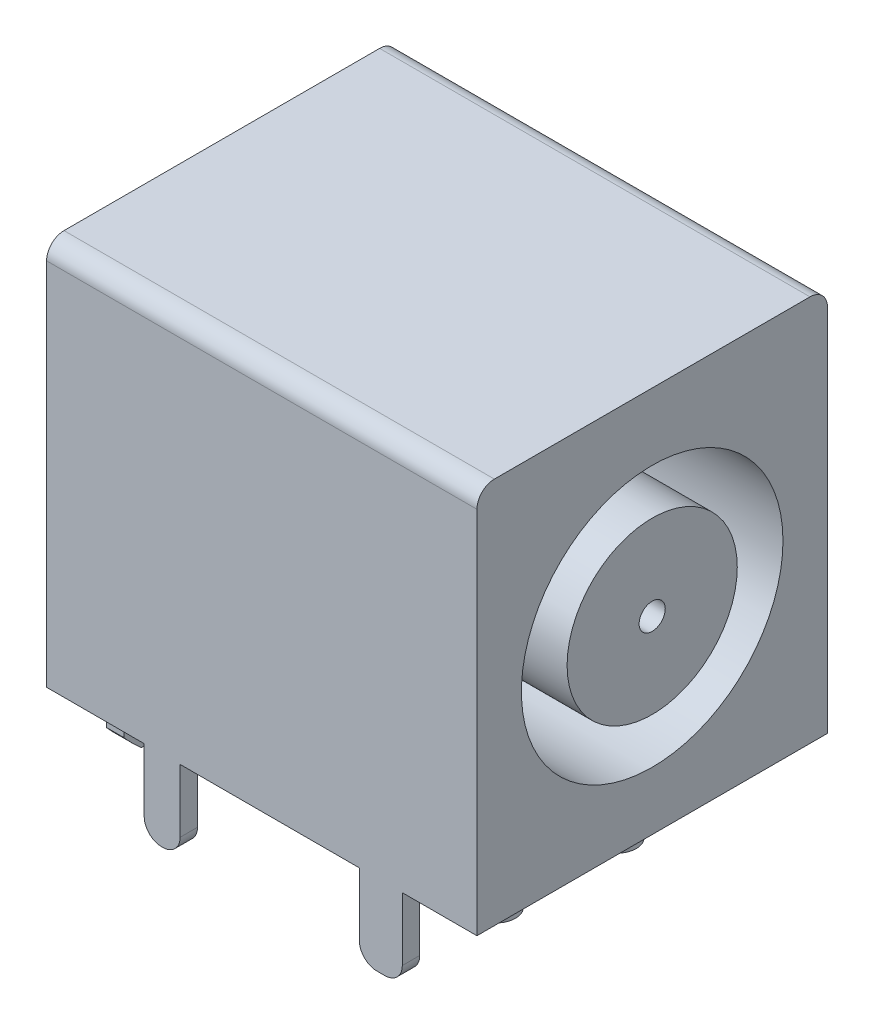
SolidWorks part; units mm, degrees
ref_plane "Front Plane" through (0, 0, 0) normal (0, 0, 1) x (1, 0, 0)
ref_plane "Top Plane" through (0, 0, 0) normal (0, 1, 0) x (1, 0, 0)
ref_plane "Right Plane" through (0, 0, 0) normal (1, 0, 0) x (0, 0, -1)
other "MetalWidth"
sketch "Sketch1" plane through (0, 0, 0) normal (0, 1, 0) x (1, 0, 0)
  line L1 (-6.17, 5.025) -> (6.17, 5.025)
  line L2 (-6.17, 5.025) -> (-6.17, -5.025)
  line L3 (-6.17, -5.025) -> (6.17, -5.025)
  line L4 (6.17, 5.025) -> (6.17, -5.025)
  line L5 (-6.17, 5.025) -> (6.17, -5.025) construction
  line L6 (-6.17, -5.025) -> (6.17, 5.025) construction
  point P0 (0, 0)
  dimension "D1" = 10.05
  dimension "D2" = 12.34
extrude "Boss-Extrude1" add sketch "Sketch1" along normal blind 11.09
sketch "Sketch2" plane through (6.17, 0, 0) normal (1, 0, 0) x (0, 0, -1)
  line L0 (0, 0) -> (0, 11.09) construction
  line L1 (-5.025, 0) -> (5.025, 0) construction
  line L2 (-5.025, 11.09) -> (5.025, 11.09) construction
  circle A0 centre (0, 5.42) radius 3.75
  point P6 (0, 1.53)
  point P7 (0, 1.67)
  point P8 (0, 0)
  dimension "D1" = 1.67
  dimension "D2" = 7.5
extrude "Cut-Extrude1" cut sketch "Sketch2" against normal blind 5
sketch "Sketch4" plane through (1.17, 0, 0) normal (1, 0, 0) x (0, 0, -1)
  circle A0 centre (0, 5.42) radius 2.44
  dimension "D1" = 4.88
extrude "Boss-Extrude2" add sketch "Sketch4" along normal up to surface (5 mm away) up to face at (6.17, 5.42, -3.75)
sketch "Sketch6" plane through (6.17, 0, 0) normal (1, 0, 0) x (0, 0, -1)
  circle A0 centre (0, 5.42) radius 0.375
  dimension "D1" = 0.75
extrude "Cut-Extrude2" cut sketch "Sketch6" against normal blind 8
sketch "Sketch12" plane through (0, 11.09, 0) normal (0, 1, 0) x (1, 0, 0)
  line L0 (-6.17, 0) -> (6.17, 0) construction
  line L3 (-6.17, 5.025) -> (-6.17, -5.025) construction
  point P7 (-10, -0.303)
sketch "Sketch13" plane through (0, 0, 0) normal (0, -1, 0) x (1, 0, 0)
  line L0 (-6.17, 0) -> (6.17, 0) construction
  line L1 (-6.17, 5.025) -> (6.17, 5.025) construction
  line L2 (4.03, 5.025) -> (2.8, 5.025)
  line L3 (4.03, 5.025) -> (4.03, 4.525)
  line L4 (4.03, 4.525) -> (2.8, 4.525)
  line L5 (2.8, 5.025) -> (2.8, 4.525)
  line L6 (-5.62, -3.355) -> (-5.62, -2.155)
  line L7 (-3.37, 5.025) -> (-2.34, 5.025)
  line L8 (-3.37, 5.025) -> (-3.37, 4.525)
  line L9 (-3.37, 4.525) -> (-2.34, 4.525)
  line L10 (-2.34, 5.025) -> (-2.34, 4.525)
  line L11 (-6.12, 3.355) -> (-5.62, 3.355)
  line L12 (-6.12, 3.355) -> (-6.12, 2.155)
  line L13 (-6.12, 2.155) -> (-5.62, 2.155)
  line L14 (-5.62, 3.355) -> (-5.62, 2.155)
  line L15 (-3.27, 0.6) -> (-2.8143, 0.6)
  line L16 (-3.27, 0.6) -> (-3.27, -0.6)
  line L17 (-3.27, -0.6) -> (-2.8143, -0.6)
  line L18 (-2.8143, 0.6) -> (-2.8143, -0.6)
  line L19 (0.7257, 0.6) -> (1.1857, 0.6)
  line L20 (0.7257, 0.6) -> (0.7257, -0.6)
  line L21 (0.7257, -0.6) -> (1.1857, -0.6)
  line L22 (1.1857, 0.6) -> (1.1857, -0.6)
  line L23 (6.17, 5.025) -> (6.17, -5.025) construction
  line L24 (3.425, 2.285) -> (7.5311, 2.285) construction
  line L25 (2.87, 1.73) -> (2.87, -0.7627) construction
  line L26 (6.17, -3.75) -> (6.17, 3.75) construction
  line L27 (-6.12, -2.155) -> (-5.62, -2.155)
  line L28 (-6.12, -3.355) -> (-6.12, -2.155)
  line L29 (-6.12, -3.355) -> (-5.62, -3.355)
  line L30 (-2.34, -5.025) -> (-2.34, -4.525)
  line L31 (-3.37, -4.525) -> (-2.34, -4.525)
  line L32 (-3.37, -5.025) -> (-3.37, -4.525)
  line L33 (-3.37, -5.025) -> (-2.34, -5.025)
  line L34 (2.8, -5.025) -> (2.8, -4.525)
  line L35 (4.03, -4.525) -> (2.8, -4.525)
  line L36 (4.03, -5.025) -> (4.03, -4.525)
  line L37 (4.03, -5.025) -> (2.8, -5.025)
  line L38 (-6.17, -5.025) -> (-6.17, 5.025) construction
  line L39 (-6.17, 0.185) -> (-5.49, 0.185)
  line L40 (-6.17, 0.185) -> (-6.17, -0.185)
  line L41 (-6.17, -0.185) -> (-5.49, -0.185)
  line L42 (-5.49, 0.185) -> (-5.49, -0.185)
  line L43 (-6.17, 0) -> (-4.9844, 0) construction
  circle A0 centre (3.425, 1.73) radius 0.555
  circle A1 centre (3.425, -1.73) radius 0.555
  point P30 (-2.34, 4.775)
  point P37 (-3.27, 0)
  point P58 (-6.17, 0)
  dimension "D8" = 1.11
  dimension "D1" = 3.37
  dimension "D2" = 1.23
  dimension "D3" = 0.5
  dimension "D4" = 9.54
  dimension "D5" = 0.5
  dimension "D6" = 1.03
  dimension "D7" = 5.14
  dimension "D9" = 2.285
  dimension "D10" = 3.3
  dimension "D11" = 3.355
  dimension "D12" = 1.2
  dimension "D13" = 0.5
  dimension "D14" = 12.29
  dimension "D15" = 9.44
  dimension "D16" = 3.54
  dimension "D17" = 0.4557
  dimension "D18" = 1.2
  dimension "D19" = 0
  dimension "D20" = 0.46
  dimension "D21" = 1.2
  dimension "D22" = 0
  dimension "D23" = 0.37
  dimension "D24" = 0.68
extrude "Boss-Extrude3" add sketch "Sketch13" along normal blind 2.31
fillet "Fillet2" radius 0.5 8 edges at (-3.37, -2.31, 4.775) (-2.34, -2.31, 4.775) (2.8, -2.31, 4.775) (4.03, -2.31, 4.775) (-3.37, -2.31, -4.775) (-2.34, -2.31, -4.775) (2.8, -2.31, -4.775) (4.03, -2.31, -4.775)
fillet "Fillet3" radius 0.5 2 edges at (0, 11.09, -5.025) (0, 11.09, 5.025)
fillet "Fillet4" radius 0.5 8 edges at (0.9557, -2.31, -0.6) (0.9557, -2.31, 0.6) (-3.0422, -2.31, -0.6) (-3.0422, -2.31, 0.6) (-5.87, -2.31, -3.355) (-5.87, -2.31, -2.155) (-5.87, -2.31, 2.155) (-5.87, -2.31, 3.355) conic radius 10
equation "\"MetalWidth\"=0.31"
